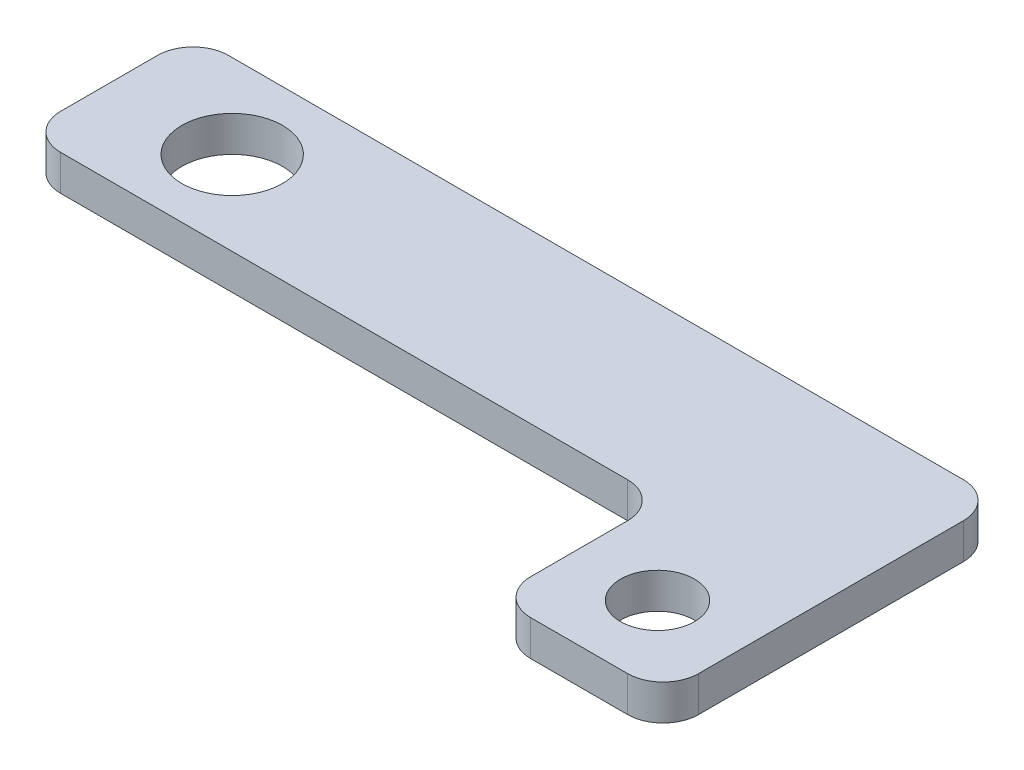
SolidWorks part; units mm, degrees
material "3003-H14"
ref_plane "X-Y Datum" through (0, 0, 0) normal (0, 0, 1) x (1, 0, 0)
ref_plane "X-Z Datum" through (0, 0, 0) normal (0, 1, 0) x (1, 0, 0)
ref_plane "Y-Z Datum" through (0, 0, 0) normal (1, 0, 0) x (0, 0, -1)
sketch "Sketch1" plane through (0, 0, 0) normal (0, 1, 0) x (1, 0, 0)
  line L0 (56, -44.0812) -> (71, -44.0812) construction
  line L1 (10, -36.0812) -> (10, -21.0812) construction
  line L2 (10, -36.0812) -> (56, -36.0812)
  line L3 (56, -36.0812) -> (56, -44.0812)
  line L4 (10, -21.0812) -> (71, -21.0812)
  line L5 (71, -21.0812) -> (71, -44.0812)
  line L6 (56, -44.0812) -> (56, -51.0812)
  line L7 (56, -51.0812) -> (71, -51.0812)
  line L8 (71, -51.0812) -> (71, -44.0812)
  line L9 (10, -21.0812) -> (-1, -21.0812)
  line L10 (-1, -21.0812) -> (-1, -36.0812)
  line L11 (-1, -36.0812) -> (10, -36.0812)
  point P0 (63.5, -44.0812)
  point P1 (10, -28.5812)
  point P7 (63.5, -44.0812)
  point P10 (10, -28.5812)
  dimension "D1" = 15
  dimension "D2" = 15
  dimension "D3" = 11
  dimension "D4" = 7
extrude "Boss-Extrude1" add sketch "Sketch1" against normal blind 3.175
hole_wizard "M8 Clearance Hole1" positions "Sketch4" profile "Sketch3" hole size "M8" standard "ANSI Metric" end condition through all
sketch "Sketch4" plane through (0, -3.175, 0) normal (0, -1, 0) x (-1, 0, 0)
  point P0 (-10, -28.5812)
sketch "Sketch3" plane through (10, -3.175, 28.5812) normal (1, 0, 0) x (0, 0, -1)
  line L0 (0, 0) -> (0, 3.175)
  line L1 (0, 3.175) -> (4.5, 3.175)
  line L2 (4.5, 3.175) -> (4.5, 0)
  line L5 (4.5, 0) -> (0, 0)
  line L11 (0, -6.35) -> (0, 107.95) construction
  dimension "Thru Hole Dia." = 9
  dimension "Thru Hole Depth" = 3.175
hole_wizard "M6 Clearance Hole1" positions "Sketch7" profile "Sketch6" hole size "M6" standard "ANSI Metric" end condition through all
sketch "Sketch7" plane through (0, -3.175, 0) normal (0, -1, 0) x (-1, 0, 0)
  point P0 (-63.5, -44.0812)
sketch "Sketch6" plane through (63.5, -3.175, 44.0812) normal (1, 0, 0) x (0, 0, -1)
  line L0 (0, 0) -> (0, 3.175)
  line L1 (0, 3.175) -> (3.3, 3.175)
  line L2 (3.3, 3.175) -> (3.3, 0)
  line L5 (3.3, 0) -> (0, 0)
  line L11 (0, -6.35) -> (0, 107.95) construction
  dimension "Thru Hole Dia." = 6.6
  dimension "Thru Hole Depth" = 3.175
fillet "Fillet1" radius 3.175 6 edges at (71, -1.5875, 21.0812) (-1, -1.5875, 21.0812) (-1, -1.5875, 36.0812) (56, -1.5875, 36.0812) (71, -1.5875, 51.0812) (56, -1.5875, 51.0812)
